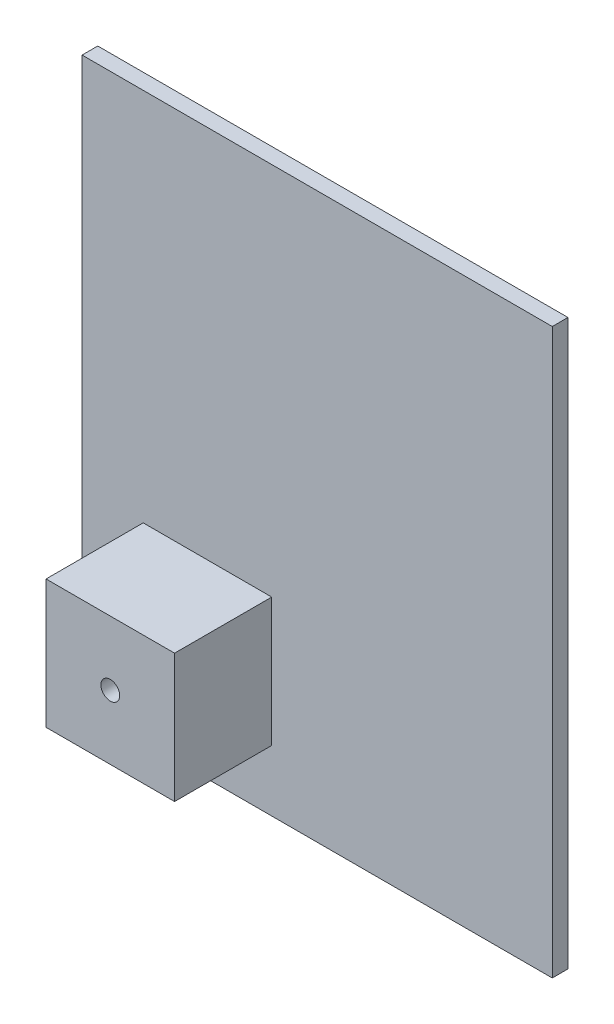
SolidWorks part; units mm, degrees
ref_plane "Front Plane" through (0, 0, 0) normal (0, 0, 1) x (1, 0, 0)
ref_plane "Top Plane" through (0, 0, 0) normal (0, 1, 0) x (1, 0, 0)
ref_plane "Right Plane" through (0, 0, 0) normal (1, 0, 0) x (0, 0, -1)
sketch "Sketch1" plane through (0, 0, 0) normal (0, 0, 1) x (1, 0, 0)
  line L1 (75, -90) -> (-75, -90)
  line L2 (75, -90) -> (75, 90)
  line L3 (75, 90) -> (-75, 90)
  line L4 (-75, -90) -> (-75, 90)
  line L5 (75, -90) -> (-75, 90) construction
  line L6 (75, 90) -> (-75, -90) construction
  line L9 (-14.5, -70.5) -> (-55.5, -70.5)
  line L10 (-14.5, -70.5) -> (-14.5, -29.5)
  line L11 (-14.5, -29.5) -> (-55.5, -29.5)
  line L12 (-55.5, -70.5) -> (-55.5, -29.5)
  line L13 (-14.5, -70.5) -> (-55.5, -29.5) construction
  line L14 (-14.5, -29.5) -> (-55.5, -70.5) construction
  circle A0 centre (-35, -50) radius 3
  point P0 (0, 0)
  dimension "D5" = 6
  dimension "D1" = 150
  dimension "D2" = 180
  dimension "D6" = 41
  dimension "D7" = 41
extrude "Boss-Extrude1" add sketch "Sketch1" along normal blind 5 contours L4 L1 L2 L3 L9 L12 L11 L10 region at (2.3237, 3.3196, 0)
extrude "Boss-Extrude2" add sketch "Sketch1<3>" along normal blind 36 contours L12 L9 L10 L11 A0 region at (-35, -69.9202, 0)
sketch "Sketch1<3>" plane through (0, 0, 0) normal (0, 0, 1) x (1, 0, 0) same geometry as "Sketch1"
extrude "Boss-Extrude3" add sketch "Sketch1<4>" against normal blind 20 separate body contours A0 region at (-35, -50, 0)
sketch "Sketch1<4>" plane through (0, 0, 0) normal (0, 0, 1) x (1, 0, 0) same geometry as "Sketch1"
